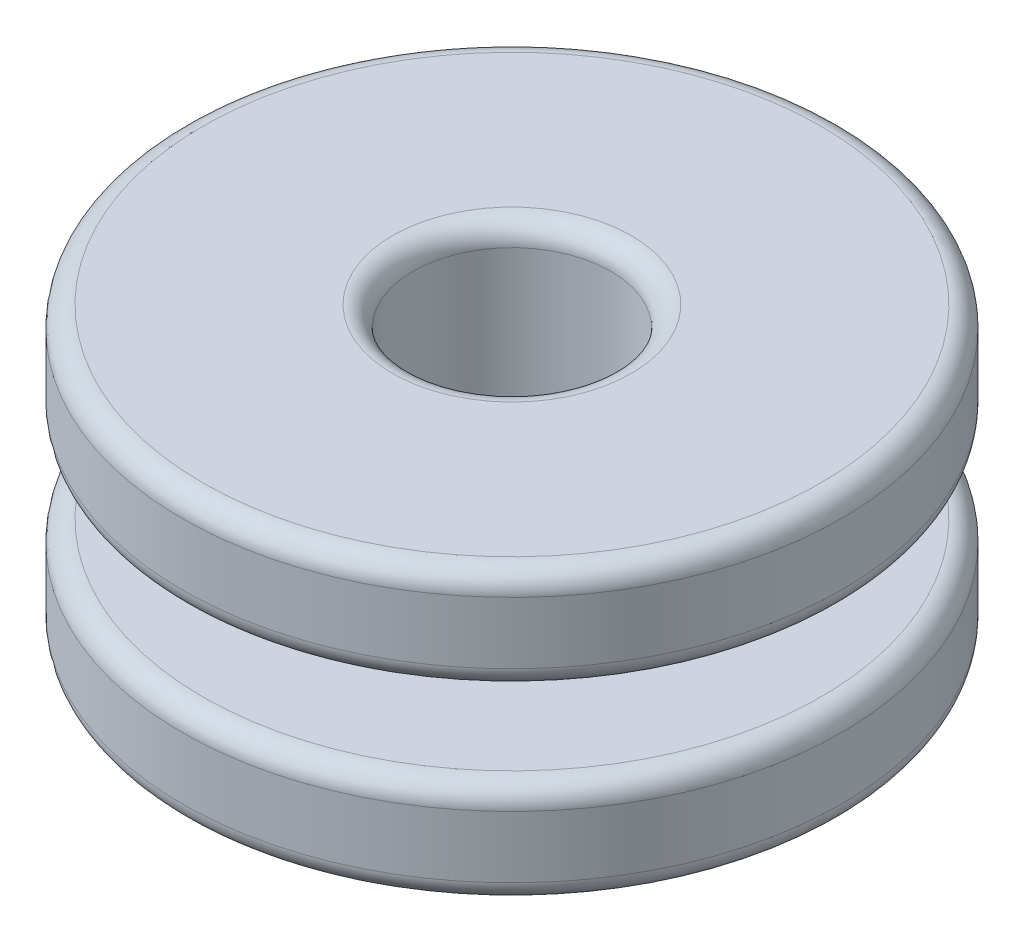
SolidWorks part; units mm, degrees
ref_plane "Front Plane" through (0, 0, 0) normal (0, 0, 1) x (1, 0, 0)
ref_plane "Top Plane" through (0, 0, 0) normal (0, 1, 0) x (1, 0, 0)
ref_plane "Right Plane" through (0, 0, 0) normal (1, 0, 0) x (0, 0, -1)
sketch "Sketch1" plane through (0, 0, 0) normal (0, 0, 1) x (1, 0, 0)
  line L0 (-1.2, 0) -> (6.8, 0) construction
  line L1 (-1.2, -3.5) -> (1.2, -3.5) construction
  line L2 (-1.2, -3.5) -> (-1.2, 3.5) construction
  line L3 (-1.2, 3.5) -> (1.2, 3.5) construction
  line L4 (1.2, -3.5) -> (1.2, 3.5)
  line L5 (-1.2, -3.5) -> (1.2, 3.5) construction
  line L6 (-1.2, 3.5) -> (1.2, -3.5) construction
  line L7 (6.8, 3.5) -> (6.8, -3.5) construction
  line L8 (1.2, 3.5) -> (6.8, 3.5)
  line L9 (1.2, 3.5) -> (1.2, -3.5)
  line L10 (1.2, -3.5) -> (6.8, -3.5)
  line L11 (6.8, 3.5) -> (6.8, 1)
  line L12 (6.8, -1) -> (6.8, -3.5)
  line L13 (1.2, 1.1727) -> (3.2, 1.1727) construction
  line L16 (3.2, 0) -> (6.8, 0) construction
  line L17 (3.2, 1) -> (6.8, 1)
  line L18 (3.2, -1) -> (6.8, -1)
  arc A5 (3.2, 1) -> (3.2, -1) centre (3.2, 0) ccw
  arc A6 (6.8, -1) -> (6.8, 1) centre (6.8, 0) ccw
  point P0 (0, 0)
  point P11 (6.8, -1)
  point P15 (5, 0)
  point P18 (3.2, 0)
  point P21 (6.8, 1)
  dimension "D4" = 5.6
  dimension "D5" = 1
  dimension "D1" = 2.4
  dimension "D2" = 7
  dimension "D3" = 8
revolve "Revolve1" add sketch "Sketch1" angle 360 about L2 region at (1.2896, 0, 0)
fillet "Fillet1" radius 0.5 6 edges at (-1.2, -3.5, -2.4) (-1.2, -3.5, -8) (-1.2, 3.5, -2.4) (-1.2, 3.5, -8) (-1.2, -1, -8) (-1.2, 1, -8)
